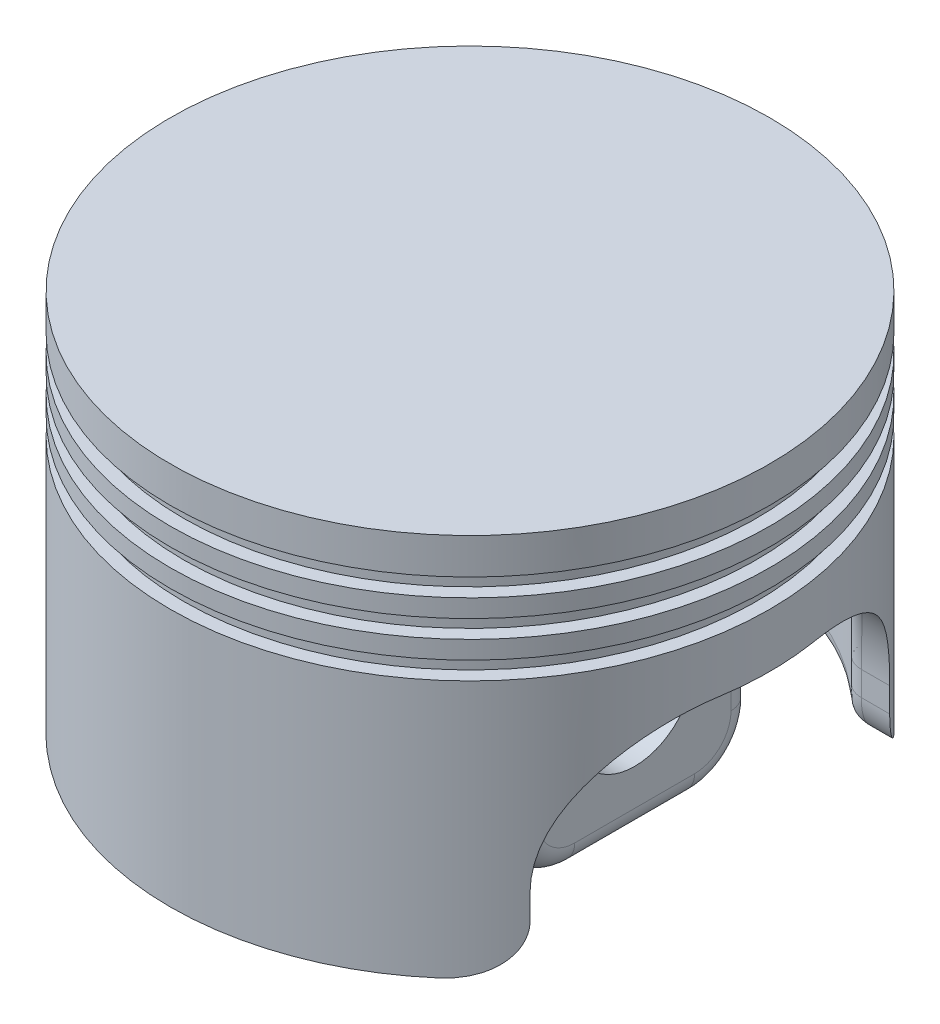
SolidWorks part; units mm, degrees
ref_plane "Front Plane" through (0, 0, 0) normal (0, 0, 1) x (1, 0, 0)
ref_plane "Top Plane" through (0, 0, 0) normal (0, 1, 0) x (1, 0, 0)
ref_plane "Right Plane" through (0, 0, 0) normal (1, 0, 0) x (0, 0, -1)
sketch "Sketch1" plane through (0, 0, 0) normal (1, 0, 0) x (0, 0, -1)
  line L0 (0, 0) -> (63.5, 0)
  line L1 (63.5, 0) -> (63.5, -81.28)
  line L2 (63.5, -81.28) -> (57.15, -81.28)
  line L3 (57.15, -81.28) -> (57.15, -19)
  line L4 (57.15, -19) -> (0, -19)
  line L5 (0, -19) -> (0, 0)
  dimension "D1" = 63.5
  dimension "D2" = 81.28
  dimension "D3" = 6.35
  dimension "D4" = 19
revolve "Revolve1" add sketch "Sketch1" angle 360 about L5
sketch "Sketch4" plane through (0, 0, 0) normal (0, 0, 1) x (1, 0, 0)
  line L4 (63.5, -7.62) -> (60.65, -7.62)
  line L5 (60.65, -7.62) -> (60.65, -11.43)
  line L6 (60.65, -11.43) -> (63.5, -11.43)
  line L7 (63.5, -11.43) -> (63.5, -7.62)
  line L8 (63.5, 0) -> (-63.5, 0) construction
  dimension "D1" = 7.62
  dimension "D2" = 3.81
  dimension "D3" = 2.85
  dimension "D4" = 63.5
ref_axis "Axis1" through (0, 4.064, 0) along (0, -1, 0)
revolve "Cut-Revolve1" cut sketch "Sketch4" angle 360 about axis through (0, 4.064, 0) along (0, -1, 0)
pattern_linear "LPattern1" count 3 spacing 7.62 along (0, -1, 0) of "Cut-Revolve1"
sketch "Sketch5" plane through (0, 0, 0) normal (1, 0, 0) x (0, 0, -1)
  line L0 (0, 4.064) -> (0, -85.344) construction
  line L1 (-38.1, -38.1) -> (38.1, -38.1)
  line L2 (-38.1, -38.1) -> (-38.1, -81.28)
  line L3 (-38.1, -81.28) -> (38.1, -81.28)
  line L4 (38.1, -38.1) -> (38.1, -81.28)
  line L5 (-38.1, -38.1) -> (38.1, -81.28) construction
  line L6 (-38.1, -81.28) -> (38.1, -38.1) construction
  line L7 (-57.15, -81.28) -> (57.15, -81.28) construction
  line L8 (63.5, 0) -> (-63.5, 0) construction
  point P0 (0, -59.69)
  dimension "D1" = 76.2
  dimension "D2" = 38.1
extrude "Cut-Extrude1" cut sketch "Sketch5" against normal mid plane 172
fillet "Fillet1" radius 28 4 edges at (46.6985, -38.1, 38.1) (46.6985, -38.1, -38.1) (-46.6985, -38.1, 38.1) (-46.6985, -38.1, -38.1)
sketch "Sketch6" plane through (0, -19, 0) normal (0, -1, 0) x (1, 0, 0)
  line L1 (-34.88, 25.4) -> (-15.88, 25.4)
  line L2 (-34.88, 25.4) -> (-34.88, -25.4)
  line L3 (-34.88, -25.4) -> (-15.88, -25.4)
  line L4 (-15.88, 25.4) -> (-15.88, -25.4)
  line L5 (-34.88, 25.4) -> (-15.88, -25.4) construction
  line L6 (-34.88, -25.4) -> (-15.88, 25.4) construction
  point P0 (-25.38, 0)
  point P5 (0, 0)
  dimension "D1" = 19
  dimension "D2" = 15.88
  dimension "D3" = 50.8
extrude "Boss-Extrude1" add sketch "Sketch6" along normal blind 63.5
mirror "Mirror1" about plane through (0, 0, 0) normal (1, 0, 0) of "Boss-Extrude1"
sketch "Sketch7" plane through (-34.88, 0, 0) normal (-1, 0, 0) x (0, 0, 1)
  line L0 (25.4, -82.5) -> (-25.4, -82.5) construction
  circle A0 centre (0, -57.1) radius 12.7
  point P4 (0, -82.5)
  dimension "D1" = 25.4
  dimension "D2" = 25.4
extrude "Cut-Extrude2" cut sketch "Sketch7" against normal blind 272.5
fillet "Fillet2" radius 12.7 4 edges at (25.38, -82.5, 25.4) (25.38, -82.5, -25.4) (-25.38, -82.5, -25.4) (-25.38, -82.5, 25.4)
fillet "Fillet3" radius 10 4 edges at (-46.6985, -81.28, -38.1) (46.6985, -81.28, -38.1) (46.6985, -81.28, 38.1) (-46.6985, -81.28, 38.1)
fillet "Fillet4" radius 5 20 edges at (15.88, -44.4, -25.4) (15.88, -78.7803, -21.6803) (15.88, -44.4, 25.4) (15.88, -78.7803, 21.6803) (34.88, -44.4, 25.4) (34.88, -78.7803, 21.6803) (34.88, -44.4, -25.4) (34.88, -78.7803, -21.6803) (-15.88, -44.4, -25.4) (-15.88, -78.7803, -21.6803) (-15.88, -44.4, 25.4) (-15.88, -78.7803, 21.6803) (-34.88, -44.4, 25.4) (-34.88, -78.7803, 21.6803) (-34.88, -44.4, -25.4) (-34.88, -78.7803, -21.6803) (15.88, -82.5, 0) (34.88, -82.5, 0) (-15.88, -82.5, 0) (-34.88, -82.5, 0)
fillet "Fillet5" radius 5 16 edges at (41.3657, -76.2692, 39.4335) (42.5971, -68.69, 38.1) (50.4318, -43.6881, 26.8841) (57.15, -38.1, 0) (46.055, -51.2516, -33.8387) (42.5971, -68.69, -38.1) (40.0022, -78.1316, -40.816) (0, -81.28, -57.15) (-41.3657, -76.2692, -39.4335) (-42.5971, -68.69, -38.1) (-50.4318, -43.6881, -26.8841) (-57.15, -38.1, 0) (-46.055, -51.2516, 33.8387) (-42.5971, -68.69, 38.1) (-40.0022, -78.1316, 40.816) (0, -81.28, 57.15)
